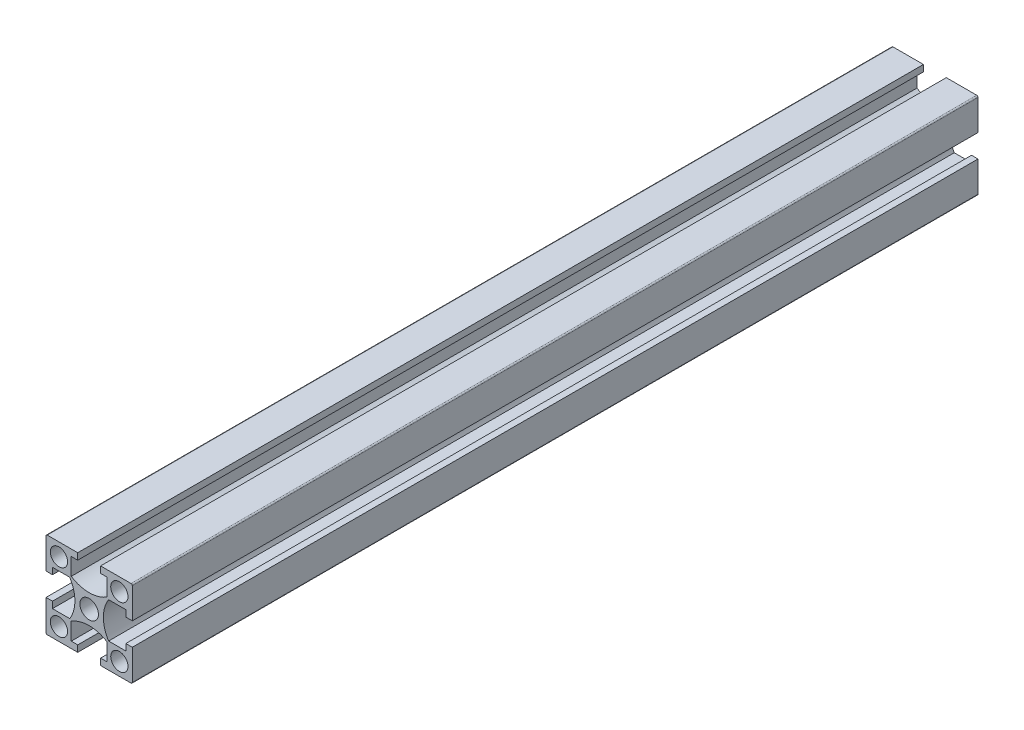
SolidWorks part; units mm, degrees
ref_plane "정면" through (0, 0, 0) normal (0, 0, 1) x (1, 0, 0)
ref_plane "윗면" through (0, 0, 0) normal (0, 1, 0) x (1, 0, 0)
ref_plane "우측면" through (0, 0, 0) normal (1, 0, 0) x (0, 0, -1)
sketch "스케치1" plane through (0, 0, 0) normal (0, 0, 1) x (1, 0, 0)
  line L0 (0, 32.0265) -> (0, -31.6588) construction
  line L1 (-10, 10) -> (-10, -10)
  line L2 (-10, 10) -> (10, 10)
  line L3 (-10, 2.65) -> (-8.5, 2.65)
  line L4 (13.6618, 0) -> (-11.6993, 0) construction
  line L5 (-8.5, 2.65) -> (-8.5, 4.15)
  line L6 (-8.5, 4.15) -> (-4.5032, 4.15)
  line L7 (-10, -2.65) -> (-8.5, -2.65)
  line L8 (-8.5, -2.65) -> (-8.5, -4.15)
  line L9 (-8.5, -4.15) -> (-4.5032, -4.15)
  line L10 (-10, -10) -> (10, -10)
  line L11 (10, 10) -> (10, -10)
  circle A0 centre (-7, 7) radius 2
  circle A1 centre (-7, -7) radius 2
  arc A2 (-4.5032, 4.15) -> (-4.5032, -4.15) centre (-11.0587, 0) cw
  circle A3 centre (0, 0) radius 2.15
  circle A4 centre (7, 7) radius 2
  circle A5 centre (7, -7) radius 2
  point P21 (-10, 0)
  point P23 (-3.3, 0)
  point P31 (0, -10)
  point P32 (0, 10)
  dimension "D3" = 4
  dimension "D9" = 6.7
  dimension "D10" = 4.3
  dimension "D11" = 7.7587
  dimension "D1" = 20
  dimension "D2" = 20
  dimension "D4" = 14
  dimension "D5" = 14
  dimension "D6" = 5.3
  dimension "D7" = 8.3
  dimension "D8" = 1.5
extrude "보스-돌출1" add sketch "스케치1" along normal blind 196 contours A0 | A4 | A3 | A5 | A1 | A2 L6 L5 L3 L1 L7 L8 L9 | L2 L11 L10 L1 region at (-6.6069, 0, 0) region at (-7, 7, 0) region at (-7, -7, 0) region at (0, 0, 0) region at (7, 7, 0) region at (7, -7, 0)
extrude "컷-돌출1" cut sketch "스케치1<3>" along normal up to next contours A2 L6 L5 L3 L1 L7 L8 L9 region at (-6.6069, 0, 0)
sketch "스케치1<3>" plane through (0, 0, 0) normal (0, 0, 1) x (1, 0, 0) same geometry as "스케치1"
pattern_circular "원형 패턴1" count 4 over 360 about axis through (0, 0, 196) along (0, 0, -1) of "컷-돌출1" reverse direction yes
fillet "필렛1" radius 0.3 4 edges at (10, -10, 98) (-10, -10, 98) (-10, 10, 98) (10, 10, 98)
sketch "스케치2" plane through (-10, 0, 0) normal (-1, 0, 0) x (0, 0, 1)
  line L0 (0, 4.15) -> (0, -4.15) construction
  line L1 (196, -4.15) -> (196, 4.15) construction
  circle A0 centre (11, 0) radius 2.5
  circle A1 centre (185, 0) radius 2.5
  dimension "D1" = 11
  dimension "D2" = 11
extrude "컷-돌출2" cut sketch "스케치2" against normal through all
sketch "스케치4" plane through (0, -10, 0) normal (0, -1, 0) x (1, 0, 0)
  line L1 (4.15, 196) -> (-4.15, 196) construction
  circle A0 centre (0, 98) radius 2.5
  dimension "D1" = 98
extrude "컷-돌출4" cut sketch "스케치4" against normal through all
